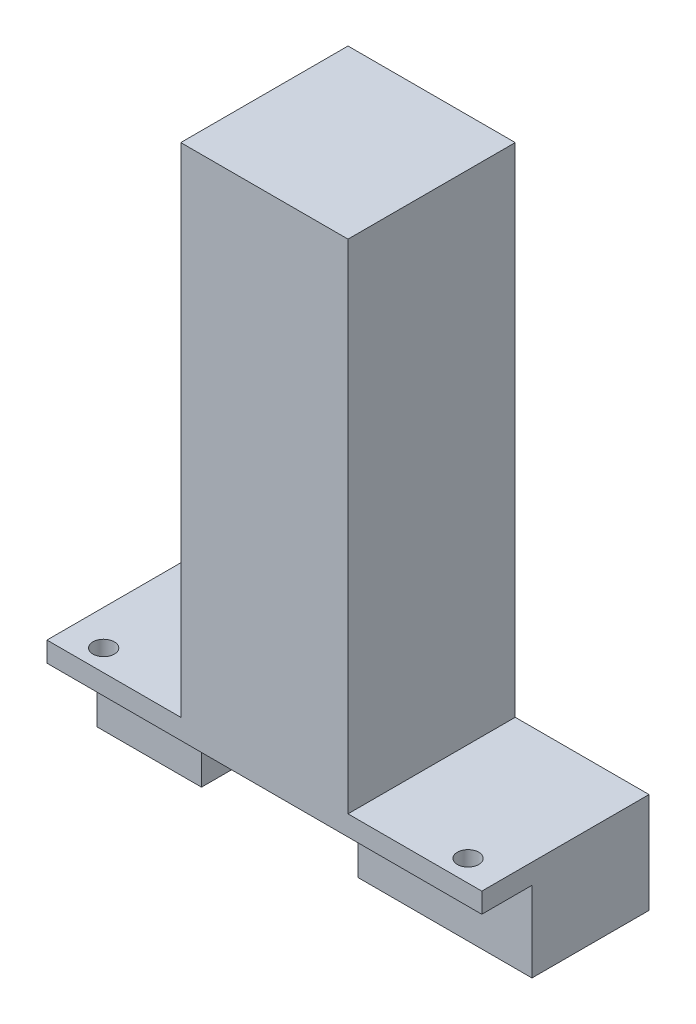
SolidWorks part; units mm, degrees
ref_plane "Front Plane" through (0, 0, 0) normal (0, 0, 1) x (1, 0, 0)
ref_plane "Top Plane" through (0, 0, 0) normal (0, 1, 0) x (1, 0, 0)
ref_plane "Right Plane" through (0, 0, 0) normal (1, 0, 0) x (0, 0, -1)
sketch "Sketch2" plane through (0, 0, 0) normal (0, 1, 0) x (1, 0, 0)
  line L1 (-32.5, -12.5) -> (32.5, -12.5)
  line L2 (-32.5, -12.5) -> (-32.5, 12.5)
  line L3 (-32.5, 12.5) -> (32.5, 12.5)
  line L4 (32.5, -12.5) -> (32.5, 12.5)
  line L5 (-32.5, -12.5) -> (32.5, 12.5) construction
  line L6 (-32.5, 12.5) -> (32.5, -12.5) construction
  point P0 (0, 0)
  dimension "D1" = 65
  dimension "D2" = 25
extrude "Boss-Extrude1" add sketch "Sketch2" along normal blind 3
sketch "Sketch3" plane through (0, 0, 0) normal (0, -1, 0) x (1, 0, 0)
  line L0 (32.5, -12.5) -> (-32.5, -12.5) construction
  line L1 (-32.5, 5) -> (-16.9, 5)
  line L2 (-32.5, 5) -> (-32.5, -12.5)
  line L3 (-32.5, -12.5) -> (-16.9, -12.5)
  line L4 (-16.9, 5) -> (-16.9, -12.5)
  line L10 (32.5, 5) -> (6.5, 5)
  line L12 (6.5, 5) -> (6.5, 0)
  line L13 (6.5, 0) -> (12.5, 0)
  line L14 (12.5, 0) -> (12.5, -12.5)
  line L15 (32.5, -12.5) -> (-32.5, -12.5) construction
  line L16 (12.5, -12.5) -> (32.5, -12.5)
  line L17 (32.5, -12.5) -> (32.5, 5)
  line L18 (-32.5, -12.5) -> (-32.5, 12.5) construction
  point P9 (0, 0)
  point P10 (0, 0)
  point P16 (0, 0)
  point P22 (0, 0)
  point P23 (0, 0)
  dimension "D1" = 15.6
  dimension "D2" = 26
  dimension "D3" = 20
  dimension "D4" = 17.5
extrude "Boss-Extrude2" add sketch "Sketch3" along normal blind 12
sketch "Sketch5" plane through (0, 3, 0) normal (0, 1, 0) x (1, 0, 0)
  circle A0 centre (27.2349, -9.2897) radius 1.6
  circle A1 centre (-27.2349, -9.2897) radius 1.6
  circle A2 centre (27.2349, -9.2897) radius 1.6 construction
extrude "Cut-Extrude1" cut sketch "Sketch5" against normal through all
sketch "Sketch6" plane through (0, 3, 0) normal (0, 1, 0) x (1, 0, 0)
  line L0 (-32.5, -12.5) -> (32.5, -12.5) construction
  line L1 (12.5, -12.5) -> (-12.5, -12.5)
  line L2 (12.5, -12.5) -> (12.5, 12.5)
  line L3 (12.5, 12.5) -> (-12.5, 12.5)
  line L4 (-12.5, -12.5) -> (-12.5, 12.5)
  line L5 (32.5, 12.5) -> (-32.5, 12.5) construction
  line L6 (0, -20.7065) -> (0, 20.7065) construction
  point P12 (0, 0)
  dimension "D1" = 25
extrude "Boss-Extrude3" add sketch "Sketch6" along normal blind 74.4
sketch "Sketch7" plane through (12.5, 0, 0) normal (1, 0, 0) x (0, 0, -1)
  line L0 (12.5, 77.4) -> (12.5, 3) construction
  line L1 (-12.5, 77.4) -> (12.5, 77.4) construction
  line L2 (-12.5, 77.4) -> (-12.5, 3) construction
  circle A0 centre (0, 64.9) radius 12.5
  point P8 (0, 0)
sketch "Sketch8" plane through (-12.5, 0, 0) normal (-1, 0, 0) x (0, 0, 1)
  circle A0 centre (0, 64.9) radius 12.5 construction
  circle A1 centre (0, 64.9) radius 12.5
  point P3 (0, 0)
ref_axis "Axis1" through (-18.9714, 64.9, 0) along (1, 0, 0)
